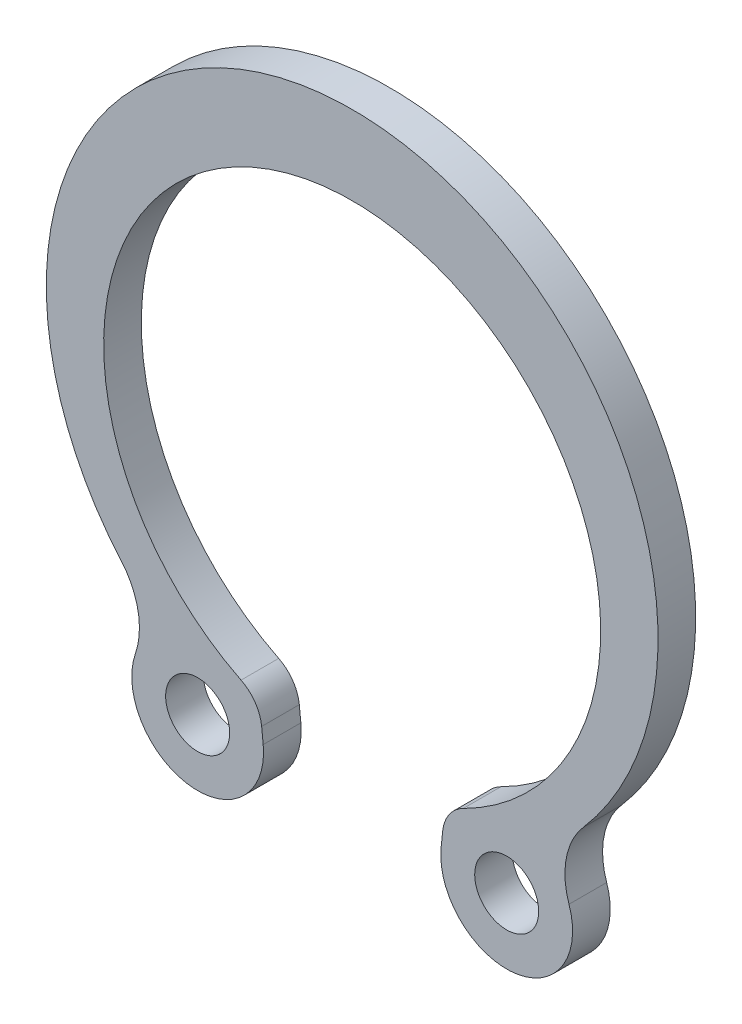
SolidWorks part; units mm, degrees
ref_plane "Спереди" through (0, 0, 0) normal (0, 0, 1) x (1, 0, 0)
ref_plane "Сверху" through (0, 0, 0) normal (0, 1, 0) x (1, 0, 0)
ref_plane "Справа" through (0, 0, 0) normal (1, 0, 0) x (0, 0, -1)
sketch "Эскиз1" plane through (0, 0, 0) normal (0, 0, 1) x (1, 0, 0)
  line L0 (0, -1000) -> (0, 49000) construction
  line L1 (3, -6.6841) -> (3, -6.2851)
  arc A0 (3.4631, -5.4415) -> (0, 6.45) centre (0, 0) ccw
  circle A2 centre (0, 0) radius 7 construction
  circle A3 centre (0, 0) radius 11 construction
  circle A4 centre (0, 0) radius 6.6 construction
  circle A5 centre (4.75, -6.6841) radius 0.85
  arc A7 (3, -6.6841) -> (6.3374, -5.9475) centre (4.75, -6.6841) ccw
  arc A8 (6.5131, -3.9588) -> (6.3374, -5.9475) centre (8.1516, -5.1056) ccw
  arc A9 (3.4631, -5.4415) -> (3, -6.2851) centre (4, -6.2851) ccw
  arc A10 (6.5131, -3.9588) -> (0, 8.55) centre (0, 0.6) ccw
  circle A12 centre (0, 0.6) radius 7.95 construction
  dimension "_d2" = 12.9
  dimension "_d3" = 15.9
  dimension "_d" = 14
  dimension "_D_" = 22
  dimension "_d1" = 13.2
  dimension "_d4" = 1.7
  dimension "_a" = 3.5
  dimension "_r1" = 2
  dimension "_r2" = 1
  dimension "_e" = 0.6
  dimension "_l" = 3
sketch "Эскиз2" plane through (0, 0, 0) normal (0, 0, 1) x (1, 0, 0)
  line L0 (0, -201000) -> (0, 249000) construction
  line L1 (0, -998.9795) -> (0, 49001.0205) construction
  line L2 (0, 0) -> (3.4631, -5.4415) construction
  line L3 (0, 0) -> (-2.9515, -5.9033) construction
  line L4 (0, 6.6) -> (0, 8.7)
  line L5 (3.4631, -5.4415) -> (3, -6.2851) construction
  line L6 (-2.9515, -5.9033) -> (-2.404, -6.6948) construction
  line L7 (-2.404, -6.6948) -> (-2.3629, -7.0917)
  line L8 (3, -6.6841) -> (3, -6.2851) construction
  line L9 (-6.1386, -4.7433) -> (-5.7586, -6.7032) construction
  line L10 (6.5131, -3.9588) -> (6.3374, -5.9475) construction
  line L11 (0, 8.7) -> (1, 8.7) construction
  arc A0 (0, 6.6) -> (-2.9515, -5.9033) centre (0, 0) ccw
  circle A1 centre (0, 0) radius 6.6 construction
  circle A2 centre (-4.1036, -7.2721) radius 0.85
  circle A3 centre (4.75, -6.6841) radius 0.85 construction
  arc A4 (-5.7586, -6.7032) -> (-2.3629, -7.0917) centre (-4.1036, -7.2721) ccw
  arc A5 (3, -6.6841) -> (6.3374, -5.9475) centre (4.75, -6.6841) ccw construction
  arc A6 (-2.9515, -5.9033) -> (-2.404, -6.6948) centre (-3.3987, -6.7977) cw
  arc A7 (3.4631, -5.4415) -> (3, -6.2851) centre (4, -6.2851) ccw construction
  arc A8 (0, 8.7) -> (-6.1386, -4.7433) centre (0, 0.5768) ccw
  arc A9 (-5.7586, -6.7032) -> (-6.1386, -4.7433) centre (-7.6499, -6.0531) ccw
  arc A10 (6.5131, -3.9588) -> (6.3374, -5.9475) centre (8.1516, -5.1056) ccw construction
  dimension "D1" = 147.526
  dimension "D2" = 6.45
  dimension "D3" = 6.6
  dimension "D4" = 153.436
  dimension "_b" = 2.1
  dimension "_s" = 1
extrude "Бобышка-Вытянуть1" add sketch "Эскиз2" along normal blind 1
mirror "Зеркальное отражение1" about plane through (0, 6.6, 1) normal (-1, 0, 0) of bodies 103
sketch "Эскиз3" plane through (0, 0, 0) normal (0, 0, 1) x (1, 0, 0)
  circle A0 centre (0, 0) radius 6.6 construction
  circle A1 centre (0, 0) radius 11 construction
  circle A2 centre (0, 0) radius 6.6 construction
  circle A3 centre (0, 0) radius 11 construction
sketch "Эскиз4" plane through (0, 0, 0) normal (1, 0, 0) x (0, 0, -1)
  line L0 (-1, 8.7) -> (0.2, 8.7)
  dimension "_m" = 1.2
equation "\"D4@Эскиз2\"=\"D1@Эскиз2\"*\"D2@Эскиз2\"/\"D3@Эскиз2\""
equation "\"D1@Бобышка-Вытянуть1\"= \"_s@Эскиз2\""
